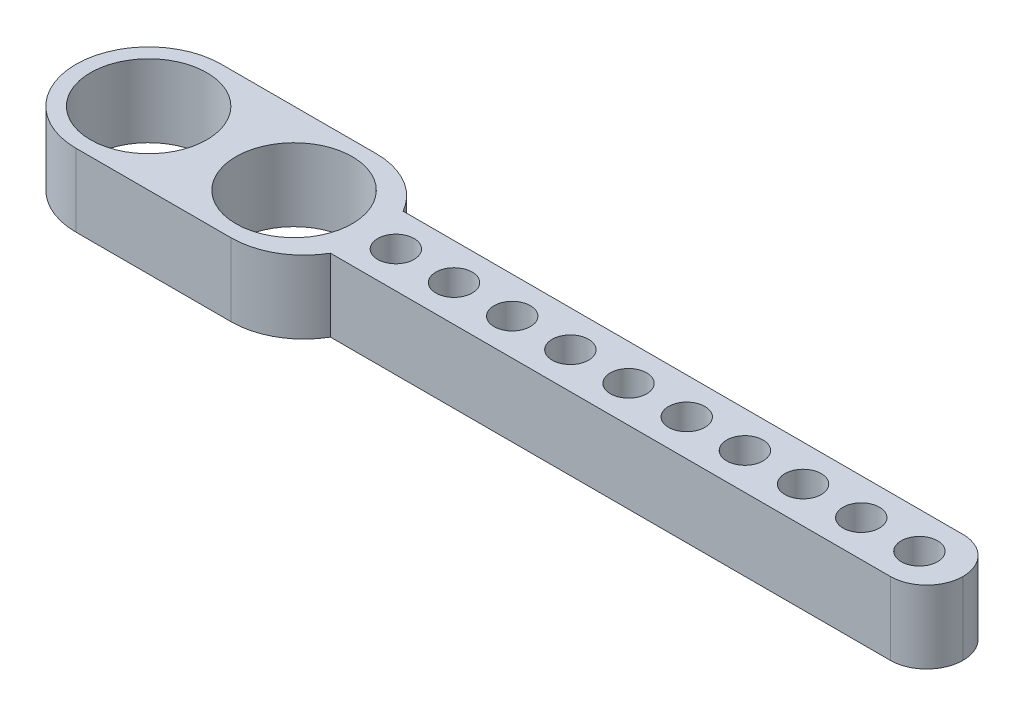
SolidWorks part; units mm, degrees
ref_plane "Front Plane" through (0, 0, 0) normal (0, 0, 1) x (1, 0, 0)
ref_plane "Top Plane" through (0, 0, 0) normal (0, 1, 0) x (1, 0, 0)
ref_plane "Right Plane" through (0, 0, 0) normal (1, 0, 0) x (0, 0, -1)
sketch "Sketch1" plane through (0, 0, 0) normal (0, 1, 0) x (1, 0, 0)
  line L0 (6.35, 6.35) -> (19.05, 6.35) construction
  line L1 (0, 0) -> (25.4, 0)
  line L2 (0, 0) -> (0, 12.7)
  line L3 (0, 12.7) -> (25.4, 12.7)
  line L4 (25.4, 0) -> (25.4, 12.7)
  line L5 (27.94, 6.35) -> (33.02, 6.35) construction
  line L6 (25.4, 9.525) -> (77.47, 9.525)
  line L7 (25.4, 9.525) -> (25.4, 3.175)
  line L8 (25.4, 3.175) -> (77.47, 3.175)
  line L9 (77.47, 9.525) -> (77.47, 3.175)
  circle A0 centre (6.35, 6.35) radius 5.08
  circle A1 centre (19.05, 6.35) radius 5.08
  circle A2 centre (27.94, 6.35) radius 1.5875
  circle A3 centre (33.02, 6.35) radius 1.5875
  circle A4 centre (38.1, 6.35) radius 1.5875
  circle A5 centre (43.18, 6.35) radius 1.5875
  circle A6 centre (48.26, 6.35) radius 1.5875
  circle A7 centre (53.34, 6.35) radius 1.5875
  circle A8 centre (58.42, 6.35) radius 1.5875
  circle A9 centre (63.5, 6.35) radius 1.5875
  circle A10 centre (68.58, 6.35) radius 1.5875
  circle A11 centre (73.66, 6.35) radius 1.5875
  point P15 (77.47, 6.35)
  point P16 (25.4, 6.35)
  dimension "D2" = 10.16
  dimension "D4" = 6.35
  dimension "D5" = 6.35
  dimension "D6" = 12.7
  dimension "D9" = 3.175
  dimension "D10" = 2.54
  dimension "D11" = 5.08
  dimension "D1" = 25.4
  dimension "D3" = 12.7
  dimension "D7" = 6.35
  dimension "D8" = 52.07
extrude "Boss-Extrude1" add sketch "Sketch1" along normal blind 6.35 contours L1 L4 L3 L2 A1 A0 | L9 L6 L4 L8 A11 A10 A9 A8 A7 A6 A5 A4 A3 A2 region at (12.7, 0, -6.35) region at (51.6349, 0, -6.35)
fillet "Fillet1" radius 6.35 4 edges at (25.4, 3.175, -12.7) (25.4, 3.175, 0) (0, 3.175, -12.7) (0, 3.175, 0)
fillet "Fillet2" radius 3.175 2 edges at (77.47, 3.175, -9.525) (77.47, 3.175, -3.175)
